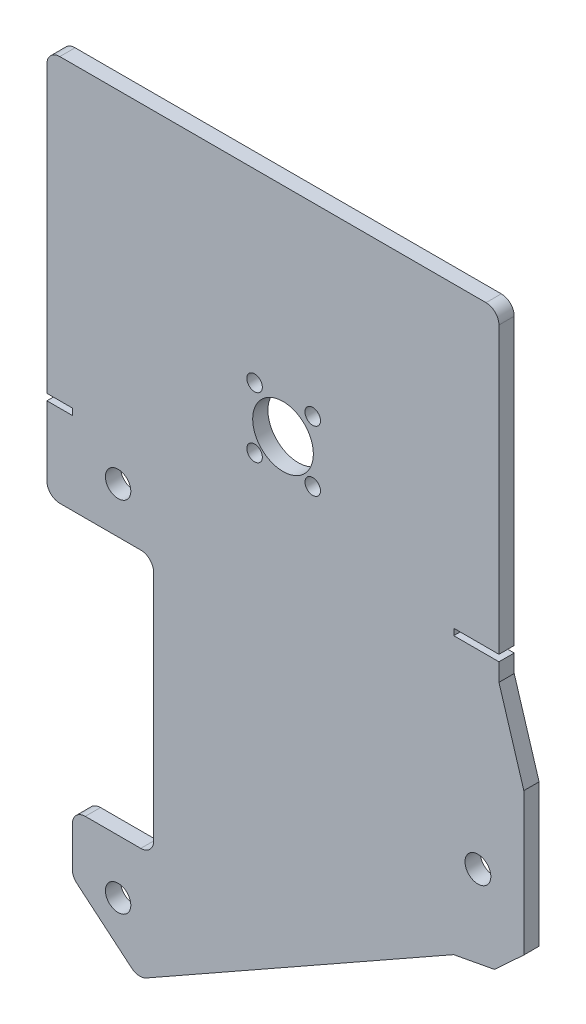
SolidWorks part; units mm, degrees
ref_plane "Front Plane" through (0, 0, 0) normal (0, 0, 1) x (1, 0, 0)
ref_plane "Top Plane" through (0, 0, 0) normal (0, 1, 0) x (1, 0, 0)
ref_plane "Right Plane" through (0, 0, 0) normal (1, 0, 0) x (0, 0, -1)
sketch "Sketch1" plane through (0, 0, 0) normal (0, 0, 1) x (1, 0, 0)
  line L0 (0, 0) -> (88.9, 0)
  line L1 (88.9, 0) -> (88.9, -3.5)
  line L2 (88.9, -3.5) -> (93.7917, -19.5)
  line L3 (93.7917, -19.5) -> (93.7917, -47.5)
  line L4 (0, 0) -> (0, -16.2)
  line L5 (0, -16.2) -> (21, -16.2)
  line L6 (21, -16.2) -> (21, -67)
  line L7 (21, -67) -> (5, -67)
  line L8 (5, -67) -> (5, -78.5)
  line L9 (5, -78.5) -> (18, -89.4083)
  line L10 (18, -89.4083) -> (80, -54.3304)
  line L11 (80, -54.3304) -> (88, -52.8477)
  line L12 (88, -52.8477) -> (93.7917, -47.5)
  dimension "D1" = 88.9
  dimension "D2" = 3.5
  dimension "D3" = 163
  dimension "D4" = 16
  dimension "D5" = 28
  dimension "D6" = 89.4083
  dimension "D7" = 21
  dimension "D8" = 50.8
  dimension "D9" = 16
  dimension "D10" = 11.5
  dimension "D11" = 130
  dimension "D12" = 13
  dimension "D13" = 110.5
  dimension "D14" = 62
  dimension "D15" = 8
  dimension "D16" = 161
extrude "Boss-Extrude1" add sketch "Sketch1" along normal blind 3
sketch "Sketch2" plane through (0, 0, 0) normal (0, 1, 0) x (1, 0, 0)
  line L0 (45.8978, 14) -> (40.3978, 14) construction
  line L1 (0, -3) -> (88.9, -3)
  line L2 (0, -3) -> (0, 54)
  line L3 (0, 54) -> (88.9, 54)
  line L4 (88.9, -3) -> (88.9, 54)
  circle A0 centre (40.3978, 8.5) radius 1.5
  circle A1 centre (40.3978, 20) radius 1.5
  circle A2 centre (51.8978, 8.5) radius 1.5
  circle A3 centre (51.8978, 20) radius 1.5
  ellipse E0 centre (45.8978, 14) end of major axis (45.8978, 8) minor radius 5.5
  dimension "D9" = 3
  dimension "D10" = 3
  dimension "D11" = 3
  dimension "D12" = 3
  dimension "D1" = 88.9
  dimension "D2" = 57
  dimension "D3" = 45.8978
  dimension "D4" = 5.5
  dimension "D5" = 11.5
  dimension "D6" = 23
  dimension "D7" = 11.5
  dimension "D8" = 17
  dimension "D13" = 12
  dimension "D14" = 11
extrude "Boss-Extrude2" add sketch "Sketch2" along normal blind 3
ref_plane "Plane1" through (85.9, 0, 0) normal (1, 0, 0) x (0, 0, -1)
sketch "Sketch3" plane through (85.9, 0, 0) normal (1, 0, 0) x (0, 0, -1)
  line L0 (11.5, 0) -> (0, 0)
  line L1 (0, 0) -> (54, 0) construction
  line L2 (0, 0) -> (0, -11.5)
  line L3 (0, -19.5) -> (0, -3.5) construction
  line L4 (0, -11.5) -> (11.5, 0)
  dimension "D1" = 11.5
  dimension "D2" = 11.5
extrude "Boss-Extrude3" add sketch "Sketch3" against normal blind 84.5
sketch "Sketch4" plane through (0, 0, 0) normal (0, 0, -1) x (-1, 0, 0)
  line L0 (-1.4, -11.5) -> (-85.9, -11.5) construction
  line L1 (-81.4, -11.5) -> (-6.4, -11.5)
  line L2 (-81.4, -11.5) -> (-81.4, 0)
  line L3 (-81.4, 0) -> (-6.4, 0)
  line L4 (-6.4, -11.5) -> (-6.4, 0)
  line L5 (-50.8976, 0) -> (-85.9, 0) construction
  line L6 (-85.9, 13.7659) -> (-85.9, -13.7659) construction
  dimension "D1" = 75
  dimension "D2" = 4.5
extrude "Cut-Extrude2" cut sketch "Sketch4" along normal blind 84.5
sketch "Sketch6" plane through (0, 0, 3) normal (0, 0, 1) x (1, 0, 0)
  line L0 (0, 3) -> (0, -16.2) construction
  line L1 (0, 3) -> (88.9, 3) construction
  circle A0 centre (14, -77.66) radius 2.5
  circle A1 centre (84.763, -37.386) radius 2.54
  circle A2 centre (14, -7.16) radius 2.5
  dimension "D1" = 5
  dimension "D2" = 5
  dimension "D3" = 5.08
  dimension "D4" = 14
  dimension "D5" = 10.16
  dimension "D6" = 70.5
  dimension "D7" = 14
  dimension "D8" = 40.386
  dimension "D9" = 70.763
extrude "Cut-Extrude3" cut sketch "Sketch6" against normal blind 84.5
sketch "Sketch7" plane through (0, 0, 0) normal (0, -1, 0) x (1, 0, 0)
  line L1 (88.9, -54) -> (0, -54)
  line L2 (88.9, -54) -> (88.9, 0)
  line L3 (88.9, 0) -> (0, 0)
  line L4 (0, -54) -> (0, 0)
extrude "Cut-Extrude4" cut sketch "Sketch7" against normal through all both and the other way through all
sketch "Sketch8" plane through (0, 0, 0) normal (0, 0, -1) x (-1, 0, 0)
  line L0 (-88.9, 3) -> (0, 3) construction
  line L1 (-88.9, 3) -> (0, 3)
  line L2 (-88.9, 3) -> (-88.9, 59.896)
  line L3 (-88.9, 59.896) -> (0, 59.896)
  line L4 (0, 3) -> (0, 59.896)
  line L5 (-46.4315, 17.1375) -> (-40.4625, 17.1375) construction
  line L6 (-14, -77.66) -> (-84.763, -77.66) construction
  line L7 (-84.763, -77.66) -> (-84.763, -37.386) construction
  line L8 (-49.3815, -77.66) -> (-49.3815, 51.3441) construction
  line L9 (-58.3815, 3) -> (-58.3815, 17.1375) construction
  line L10 (-58.3815, 17.1375) -> (-46.4315, 17.1375) construction
  circle A0 centre (-46.4315, 17.1375) radius 5.969
  circle A1 centre (-40.8435, 23.4875) radius 1.524
  circle A2 centre (-40.8435, 11.5495) radius 1.524
  circle A3 centre (-52.2735, 23.4875) radius 1.524
  circle A4 centre (-52.2735, 11.5495) radius 1.524
  dimension "D8" = 11.938
  dimension "D9" = 3.048
  dimension "D10" = 3.048
  dimension "D11" = 3.048
  dimension "D12" = 3.048
  dimension "D1" = 56.896
  dimension "D2" = 88.9
  dimension "D3" = 14.1375
  dimension "D4" = 5.588
  dimension "D5" = 2.95
  dimension "D6" = 11.938
  dimension "D7" = 5.588
  dimension "D14" = 11.43
extrude "Boss-Extrude4" add sketch "Sketch8" against normal up to surface (3 mm away) up to face at (16.5, -77.66, 3)
sketch "Sketch10" plane through (0, 0, 0) normal (0, 0, -1) x (-1, 0, 0)
  line L0 (-88.9, -3.5) -> (-88.9, 59.896) construction
  line L1 (0, 0) -> (-5.08, 0)
  line L2 (0, 0) -> (0, 1.27)
  line L3 (0, 1.27) -> (-5.08, 1.27)
  line L4 (-5.08, 0) -> (-5.08, 1.27)
  line L5 (-80.01, 0) -> (-88.9, 0)
  line L6 (-80.01, 0) -> (-80.01, 1.27)
  line L7 (-80.01, 1.27) -> (-88.9, 1.27)
  line L8 (-88.9, 0) -> (-88.9, 1.27)
  dimension "D1" = 5.08
  dimension "D2" = 1.27
  dimension "D3" = 8.89
  dimension "D4" = 1.27
extrude "Cut-Extrude5" cut sketch "Sketch10" against normal blind 10
fillet "Fillet1" radius 2.54 8 edges at (18, -89.4083, 1.5) (5, -78.5, 1.5) (5, -67, 1.5) (21, -67, 1.5) (21, -16.2, 1.5) (0, -16.2, 1.5) (0, 59.896, 1.5) (88.9, 59.896, 1.5)
